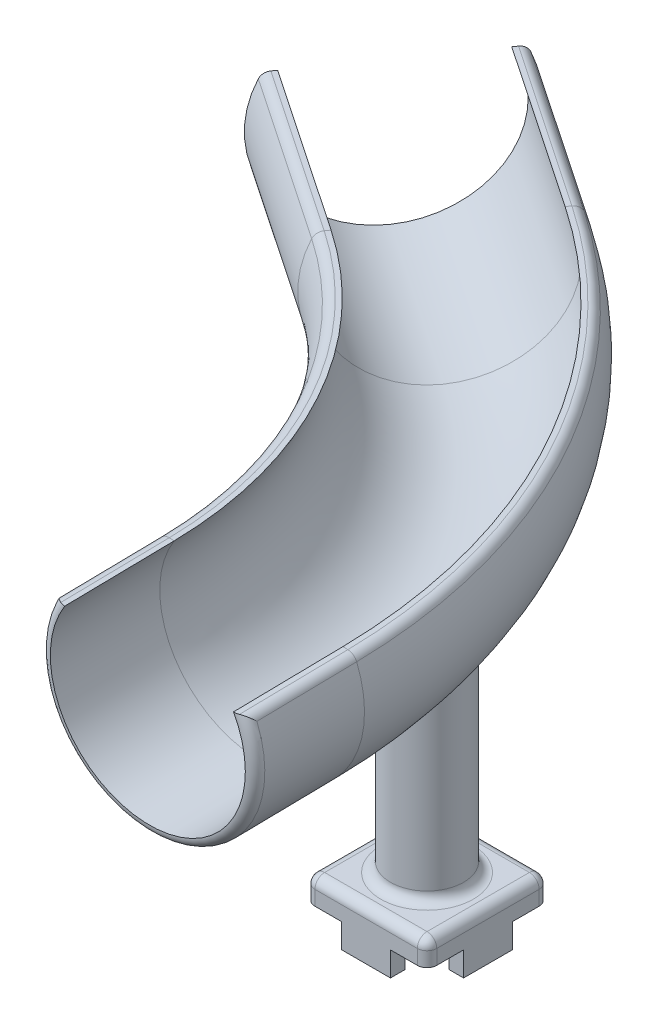
SolidWorks part; units mm, degrees
ref_plane "Front Plane" through (0, 0, 0) normal (0, 0, 1) x (1, 0, 0)
ref_plane "Top Plane" through (0, 0, 0) normal (0, 1, 0) x (1, 0, 0)
ref_plane "Right Plane" through (0, 0, 0) normal (1, 0, 0) x (0, 0, -1)
sketch "Sketch1" plane through (0, 0, 0) normal (0, 0, 1) x (1, 0, 0)
  line L0 (0, 0) -> (0, 30) construction
  dimension "D1" = 30
ref_plane "Plane1" through (0, 0, 0) normal (0.5519, 0, 0.8339) x (0, 1, 0)
ref_plane "Plane2" through (0, 0, 249) normal (0, 0, 1) x (1, 0, 0)
ref_plane "Plane3" through (182.5, 0, 0) normal (1, 0, 0) x (0, 0, -1)
ref_plane "Plane4" through (0, -8.33, 0) normal (0, 1, 0) x (1, 0, 0)
ref_point "Point2"
ref_point "Point4"
ref_point "Point6"
sketch "Sketch2" plane through (0, 0, 249) normal (0, 0, 1) x (1, 0, 0)
  point P0 (0, -4.165)
  dimension "D1" = 4.165
ref_plane "Plane5" through (0, 0, 0) normal (0.0228, 0.9996, 0.0167) x (0.9997, -0.0228, -0.0004)
sketch "Sketch4" plane through (0, 0, 0) normal (0.5519, 0, 0.8339) x (0, 1, 0)
  line L0 (0, 10.8002) -> (0, -22.3315) construction
sketch "Sketch5" plane through (0, 0, 0) normal (0.0228, 0.9996, 0.0167) x (0.9997, -0.0228, -0.0004)
  line L0 (-9.006, -5.9602) -> (18.6218, 12.3239) construction
  line L1 (-9.006, -5.9602) -> (18.6218, 12.3239) construction
  line L2 (0, 0) -> (46.9103, -70.8831) construction
  line L3 (194.5475, -245.22) -> (194.5475, -222.7649)
  line L4 (46.9103, -70.8831) -> (117.2146, -117.7108) construction
  line L5 (117.2146, -117.7108) -> (149.9832, -139.537)
  arc A0 (194.5475, -222.7649) -> (149.9832, -139.537) centre (94.5475, -222.7649) ccw
  point P8 (117.2146, -117.7108)
  point P12 (194.5475, -169.22)
  point P17 (182.5475, -249.1045)
  dimension "D5" = 100
  dimension "D1" = 85
  dimension "D2" = 76
  dimension "D3" = 84.472
  dimension "D4" = 12
ref_plane "Plane6" through (0, -63.13, 0) normal (0, 1, 0) x (1, 0, 0)
ref_plane "Plane7" through (117.1841, -4.6423, 117.6496) normal (0.8321, -0.0283, 0.554) x (0.5536, -0.019, -0.8325)
sketch "Sketch7" plane through (117.1841, -4.6423, 117.6496) normal (0.8321, -0.0283, 0.554) x (0.5536, -0.019, -0.8325)
  line L0 (-17.3205, 30) -> (-19.5959, 30)
  line L1 (19.5959, 30) -> (17.3205, 30)
  arc A0 (-17.3205, 30) -> (17.3205, 30) centre (0, 20) ccw
  arc A1 (-19.5959, 30) -> (19.5959, 30) centre (0, 20) ccw
  point P3 (0, 0)
  dimension "D1" = 20
  dimension "D2" = 22
  dimension "D3" = 30
sweep "Sweep1" add profiles "Sketch7" path "Sketch5"
sketch "Sketch8" plane through (0, -63.13, 0) normal (0, 1, 0) x (1, 0, 0)
  line L1 (170.1594, -187.97) -> (195.1594, -187.97)
  line L2 (170.1594, -187.97) -> (170.1594, -162.97)
  line L3 (170.1594, -162.97) -> (195.1594, -162.97)
  line L4 (195.1594, -187.97) -> (195.1594, -162.97)
  line L5 (170.1594, -187.97) -> (195.1594, -162.97) construction
  line L6 (170.1594, -162.97) -> (195.1594, -187.97) construction
  ellipse E0 centre (94.5229, -222.6977) end of major axis (35.4076, -303.3536) minor radius 99.96 (194.4969, -222.6595) -> (149.9442, -139.4603) ccw construction
  point P0 (182.6594, -175.47)
  point P12 (182.6594, -175.47)
  dimension "D1" = 25
  dimension "D2" = 25
extrude "Boss-Extrude1" add sketch "Sketch8" along normal blind 5 separate body
sketch "Sketch9" plane through (0, -58.13, 0) normal (0, 1, 0) x (1, 0, 0)
  circle A0 centre (182.6594, -175.47) radius 7.5
  circle A1 centre (182.6594, -175.47) radius 5.5
  ellipse E0 centre (94.5229, -222.6977) end of major axis (35.4076, -303.3536) minor radius 99.96 (194.4969, -222.6595) -> (149.9442, -139.4603) ccw construction
  point P9 (182.6594, -175.47)
  dimension "D2" = 15
  dimension "D1" = 2
extrude "Boss-Extrude2" add sketch "Sketch9" along normal up to surface (49.2088 mm away) up to face at (178.0108, 6.9567, 178.3621)
sketch "Sketch10" plane through (0, -63.13, 0) normal (0, -1, 0) x (1, 0, 0)
  line L1 (195.1594, 180.47) -> (192.1594, 180.47)
  line L2 (195.1594, 180.47) -> (195.1594, 170.47)
  line L3 (195.1594, 170.47) -> (192.1594, 170.47)
  line L4 (195.1594, 162.97) -> (195.1594, 187.97)
  line L5 (195.1594, 187.97) -> (170.1594, 187.97)
  line L6 (170.1594, 187.97) -> (170.1594, 162.97)
  line L7 (170.1594, 162.97) -> (195.1594, 162.97)
  line L8 (195.1594, 162.97) -> (195.1594, 187.97) construction
  line L9 (195.1594, 187.97) -> (170.1594, 187.97) construction
  line L10 (170.1594, 187.97) -> (170.1594, 162.97) construction
  line L11 (170.1594, 162.97) -> (195.1594, 162.97) construction
  line L12 (192.1594, 180.47) -> (192.1594, 170.47)
  line L13 (187.6594, 162.97) -> (177.6594, 162.97)
  line L14 (187.6594, 162.97) -> (187.6594, 165.97)
  line L15 (187.6594, 165.97) -> (177.6594, 165.97)
  line L16 (177.6594, 162.97) -> (177.6594, 165.97)
  line L17 (170.1594, 170.47) -> (173.1594, 170.47)
  line L18 (170.1594, 170.47) -> (170.1594, 180.47)
  line L19 (170.1594, 180.47) -> (173.1594, 180.47)
  line L20 (173.1594, 170.47) -> (173.1594, 180.47)
  line L21 (177.6594, 187.97) -> (187.6594, 187.97)
  line L22 (177.6594, 187.97) -> (177.6594, 184.97)
  line L23 (177.6594, 184.97) -> (187.6594, 184.97)
  line L24 (187.6594, 187.97) -> (187.6594, 184.97)
  point P20 (182.6594, 165.97)
  point P21 (182.6594, 184.97)
  point P22 (182.6594, 187.97)
  point P23 (192.1594, 175.47)
  point P24 (195.1594, 175.47)
  point P25 (173.1594, 175.47)
  dimension "D2" = 10
  dimension "D3" = 3
  dimension "D1" = 0
extrude "Boss-Extrude3" add sketch "Sketch10" along normal blind 5
fillet "Fillet1" radius 2 17 edges at (170.1594, -60.63, 187.97) (170.1594, -60.63, 162.97) (195.1594, -60.63, 162.97) (195.1594, -60.63, 187.97) (187.059, -9.2919, 181.544) (182.6594, -58.13, 182.97) (182.6594, -58.13, 187.97) (170.1594, -58.13, 175.47) (182.6594, -58.13, 162.97) (195.1594, -58.13, 175.47) (123.7366, 25.1564, 144.8644) (166.62, 23.5074, 184.9409) (176.2117, 22.4611, 234.4009) (215.3671, 20.7728, 234.3727) (145.4346, 24.4118, 112.2356) (201.1364, 22.2342, 166.4207) (194.4107, -10.5366, 245.0781)
